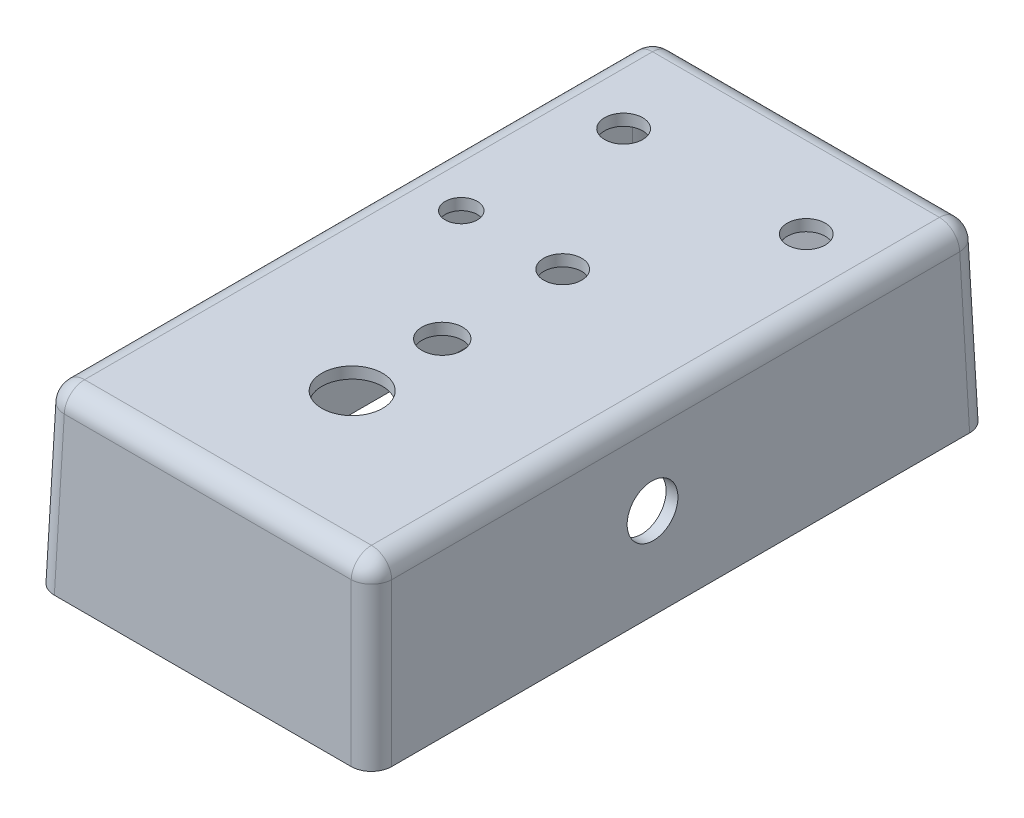
SolidWorks part; units mm, degrees
ref_plane "Front Plane" through (0, 0, 0) normal (0, 0, 1) x (1, 0, 0)
ref_plane "Top Plane" through (0, 0, 0) normal (0, 1, 0) x (1, 0, 0)
ref_plane "Right Plane" through (0, 0, 0) normal (1, 0, 0) x (0, 0, -1)
sketch "Sketch1" plane through (0, 0, 0) normal (0, 1, 0) x (1, 0, 0)
  line L1 (-33.25, -60.95) -> (33.25, -60.95)
  line L2 (-33.25, -60.95) -> (-33.25, 60.95)
  line L3 (-33.25, 60.95) -> (33.25, 60.95)
  line L4 (33.25, -60.95) -> (33.25, 60.95)
  line L5 (-33.25, -60.95) -> (33.25, 60.95) construction
  line L6 (-33.25, 60.95) -> (33.25, -60.95) construction
  point P0 (0, 0)
  dimension "D1" = 121.9
  dimension "D2" = 66.5
extrude "Box" add sketch "Sketch1" against normal blind 34.8
sketch "Sketch4" plane through (0, -34.8, 0) normal (0, -1, 0) x (1, 0, 0)
  line L9 (31, -58.7) -> (31, 58.7)
  line L10 (31, -58.7) -> (31, 58.7)
  line L11 (31, 58.7) -> (-31, 58.7)
  line L12 (31, 58.7) -> (-31, 58.7)
  line L17 (-31, 58.7) -> (-31, -58.7)
  line L18 (-31, 58.7) -> (-31, -58.7)
  line L19 (-31, -58.7) -> (31, -58.7)
  line L20 (-31, -58.7) -> (31, -58.7)
  dimension "D1" = 2.25
extrude "Hollow" cut sketch "Sketch4" against normal blind 32.55
chamfer "Side wall draft" distance 34.8 distance2 1.1 8 edges at (0, 0, 60.95) (-33.25, 0, 0) (0, 0, -60.95) (33.25, 0, 0) (-31, -2.25, 0) (0, -2.25, 58.7) (31, -2.25, 0) (0, -2.25, -58.7) first distance on face at (0, -17.4, 60.95) first distance on face at (-33.25, -17.4, 0) first distance on face at (0, -17.4, -60.95) first distance on face at (33.25, -17.4, 0) first distance on face at (-31, -18.525, 0) first distance on face at (0, -18.525, 58.7) first distance on face at (31, -18.525, 0) first distance on face at (0, -18.525, -58.7)
sketch "Sketch6" plane through (32.1179, 1.0152, 0) normal (0.9995, 0.0316, 0) x (0, 0, -1)
  line L0 (-59.85, -1.0157) -> (59.85, -1.0157) construction
  line L3 (0, -1.0157) -> (0, -39.1089) construction
  circle A0 centre (-5, -18.4157) radius 5
  dimension "D3" = 10
  dimension "D1" = 17.4
  dimension "D2" = 5
fillet "Corner rounding" radius 4 16 edges at (-32.7, -17.4, 60.4) (-32.7, -17.4, -60.4) (32.7, -17.4, -60.4) (32.7, -17.4, 60.4) (-30.4144, -18.525, -58.1144) (30.4144, -18.525, 58.1144) (30.4144, -18.525, -58.1144) (-30.4144, -18.525, 58.1144) (0, 0, -59.85) (32.15, 0, 0) (0, 0, 59.85) (-32.15, 0, 0) (29.9, -2.25, 0) (0, -2.25, -57.6) (-29.9, -2.25, 0) (0, -2.25, 57.6)
sketch "Sketch2" plane through (0, 0, 0) normal (0, 1, 0) x (1, 0, 0)
  circle A1 centre (-18, 40) radius 3.75
  circle A2 centre (0, -13.75) radius 4
  circle A3 centre (0, -31.5) radius 6
  circle A4 centre (-20, 10) radius 3.175
  circle A5 centre (18, 40) radius 3.75
  circle A8 centre (0, 10) radius 3.75
  dimension "D3" = 6.35
  dimension "D4" = 7.5
  dimension "D5" = 8
  dimension "D6" = 12
  dimension "D12" = 7.5
  dimension "D1" = 18
  dimension "D2" = 40
  dimension "D7" = 13.75
  dimension "D8" = 31.5
  dimension "D11" = 10
  dimension "D13" = 20
  dimension "D14" = 10
  dimension "D9" = 2
  dimension "D10" = 1
extrude "Top side cut" cut sketch "Sketch2" against normal blind 22.5
extrude "Input Jack" cut sketch "Sketch6" against normal blind 10
sketch "Sketch7" plane through (-32.1179, 1.0152, 0) normal (-0.9995, 0.0316, 0) x (0, 0, 1)
  line L0 (0, -4.8913) -> (0, -35.8331) construction
  line L1 (55.9744, -4.8913) -> (-55.9744, -4.8913) construction
  line L2 (-56.952, -35.8331) -> (56.952, -35.8331) construction
  line L3 (-55.9744, -0.8933) -> (55.9744, -0.8933) construction
  circle A0 centre (5, -18.2933) radius 5
  dimension "D1" = 10
  dimension "D2" = 17.4
  dimension "D3" = 5
extrude "Output Jack" cut sketch "Sketch7" against normal blind 10
equation "\"Height\" = 34.8"
equation "\"wall\"= 2.25"
equation "\"D1@Box\"=\"Height\""
equation "\"Holewidth\"=18"
equation "\"D1@Sketch2\"=\"Holewidth\""
equation "\"PotHole\"=7.5"
equation "\"D4@Sketch2\"=\"PotHole\""
equation "\"D12@Sketch2\"=\"PotHole\""
equation "\"D1@Hollow\"=\"Height\" - \"wall\""
equation "\"D1@Side wall draft\"=\"Height\""
equation "\"Jackoffset\"=5"
equation "\"D2@Sketch6\"=\"Jackoffset\""
equation "\"jackfromtop\"= \"Height\" / 2"
equation "\"D1@Sketch6\"=\"jackfromtop\""
equation "\"D3@Sketch7\"=\"Jackoffset\""
equation "\"D2@Sketch7\"=\"jackfromtop\""
